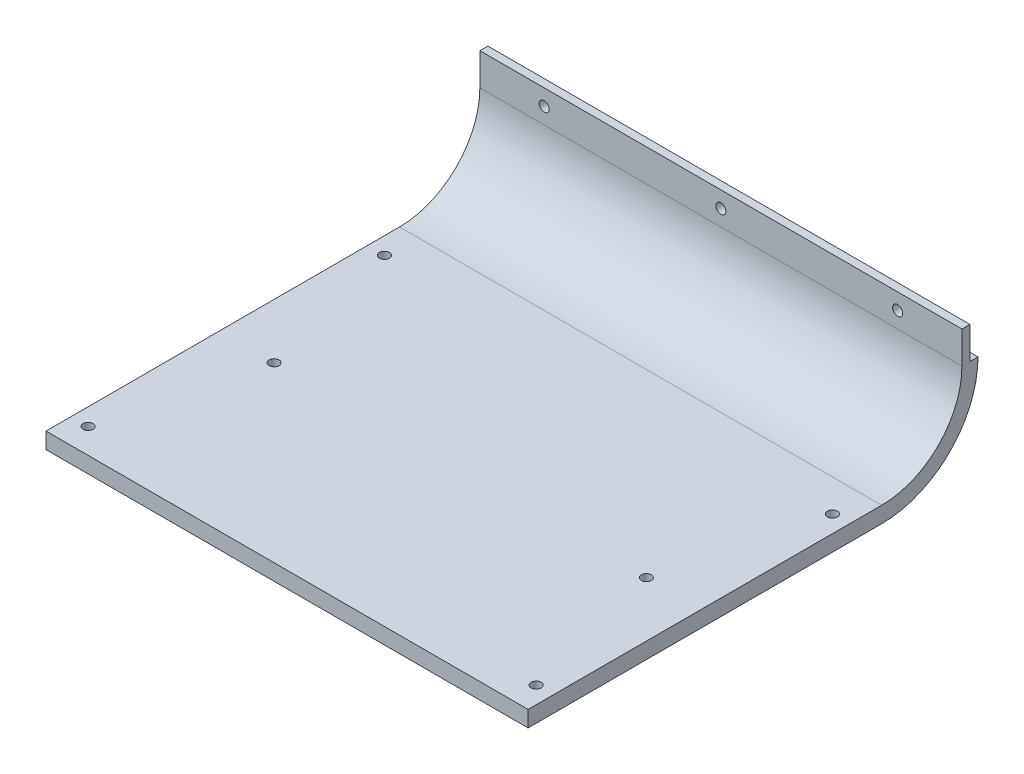
SolidWorks part; units mm, degrees
material "6061-T6 Aluminum"
ref_plane "Front Plane" through (0, 0, 0) normal (0, 0, 1) x (1, 0, 0)
ref_plane "Top Plane" through (0, 0, 0) normal (0, 1, 0) x (1, 0, 0)
ref_plane "Right Plane" through (0, 0, 0) normal (1, 0, 0) x (0, 0, -1)
sketch "Sketch1" plane through (0, 0, 0) normal (1, 0, 0) x (0, 0, -1)
  line L0 (-139.7, 0) -> (139.7, 0)
  line L5 (139.7, 0) -> (139.7, 12.7) construction
  line L7 (-139.7, 12.7) -> (139.7, 12.7)
  line L9 (-139.7, 0) -> (-139.7, 12.7)
  line L12 (139.7, 0) -> (139.7, 152.4) construction
  line L13 (0.6365, 139.0796) -> (-139.7417, 139.9778) construction
  line L14 (-12.6991, 151.8652) -> (-139.6605, 152.6775) construction
  line L15 (203.2, 76.2) -> (215.9, 76.2)
  arc A2 (139.7, 0) -> (-12.6991, 151.8652) centre (139.7, 152.4) ccw construction
  arc A3 (139.7, 12.7) -> (0.6365, 139.0796) centre (139.7, 152.4) ccw construction
  circle A5 centre (139.7, 76.2) radius 76.2 construction
  arc A6 (215.9, 76.2) -> (139.7, 0) centre (139.7, 76.2) cw
  circle A7 centre (139.7, 76.2) radius 63.5 construction
  arc A8 (203.2, 76.2) -> (139.7, 12.7) centre (139.7, 76.2) cw
  point P3 (0, 0)
  dimension "D1" = 152.4
  dimension "D2" = 12.7
  dimension "D4" = 127
  dimension "D6" = 12.7
  dimension "D3" = 12.7
  dimension "D5" = 12.7
  dimension "D7" = 355.6
extrude "Boss-Extrude1" add sketch "Sketch1" along normal blind 190.5 and the other way blind 190.5
sketch "Sketch2" plane through (0, 76.2, 0) normal (0, 1, 0) x (1, 0, 0)
  line L0 (-190.5, 215.9) -> (-190.5, 203.2) construction
  line L1 (-190.5, 209.55) -> (190.5, 209.55)
  line L2 (-190.5, 209.55) -> (-190.5, 203.2)
  line L3 (-190.5, 203.2) -> (190.5, 203.2)
  line L4 (190.5, 209.55) -> (190.5, 203.2)
extrude "Boss-Extrude2" add sketch "Sketch2" along normal blind 25.4
sketch "Sketch3" plane through (0, 0, -209.55) normal (0, 0, -1) x (-1, 0, 0)
  line L0 (-190.5, 88.9) -> (190.5, 88.9) construction
  line L1 (-190.5, 101.6) -> (-190.5, 76.2) construction
  line L2 (190.5, 101.6) -> (190.5, 76.2) construction
  line L3 (-139.7, 101.6) -> (-139.7, 76.2) construction
  line L4 (-190.5, 101.6) -> (190.5, 101.6) construction
  line L5 (-190.5, 76.2) -> (190.5, 76.2) construction
  line L6 (0, 101.6) -> (0, 76.2) construction
  line L7 (190.5, 76.2) -> (-190.5, 76.2) construction
  line L8 (139.7, 101.6) -> (139.7, 76.2) construction
  circle A0 centre (-139.7, 88.9) radius 3.9687
  circle A1 centre (139.7, 88.9) radius 3.9687
  circle A2 centre (0, 88.9) radius 3.9687
  dimension "D3" = 7.9375
  dimension "D1" = 139.7
  dimension "D2" = 139.7
extrude "Cut-Extrude1" cut sketch "Sketch3" against normal blind 25.4
sketch "Sketch4" plane through (0, 12.7, 0) normal (0, 1, 0) x (1, 0, 0)
  line L0 (0, -139.7) -> (0, -119.888) construction
  line L1 (-190.5, -139.7) -> (190.5, -139.7) construction
  line L2 (0, -119.888) -> (0, 0) construction
  line L3 (0, 0) -> (0, 114.3) construction
  line L4 (-147.066, -2.794) -> (147.066, -2.794) construction
  line L5 (-190.5, 139.7) -> (-190.5, -139.7) construction
  line L6 (-177.038, 114.3) -> (177.038, 114.3) construction
  line L8 (-177.038, -119.888) -> (177.038, -119.888) construction
  line L10 (190.5, 139.7) -> (190.5, -139.7) construction
  circle A0 centre (177.038, -119.888) radius 3.937
  circle A2 centre (177.038, 114.3) radius 3.937
  circle A3 centre (-177.038, -119.888) radius 3.937
  circle A5 centre (-177.038, 114.3) radius 3.937
  circle A6 centre (147.066, -2.794) radius 3.937
  circle A7 centre (-147.066, -2.794) radius 3.937
  point P12 (0, 114.3)
  point P14 (0, 0)
  point P15 (0, 0)
  point P19 (0, -119.888)
  dimension "D3" = 7.874
  dimension "D4" = 254
  dimension "D7" = 7.874
  dimension "D1" = 19.812
  dimension "D2" = 13.462
  dimension "D5" = 43.434
  dimension "D6" = 136.906
  dimension "D8" = 43.434
extrude "Cut-Extrude2" cut sketch "Sketch4" against normal through all
